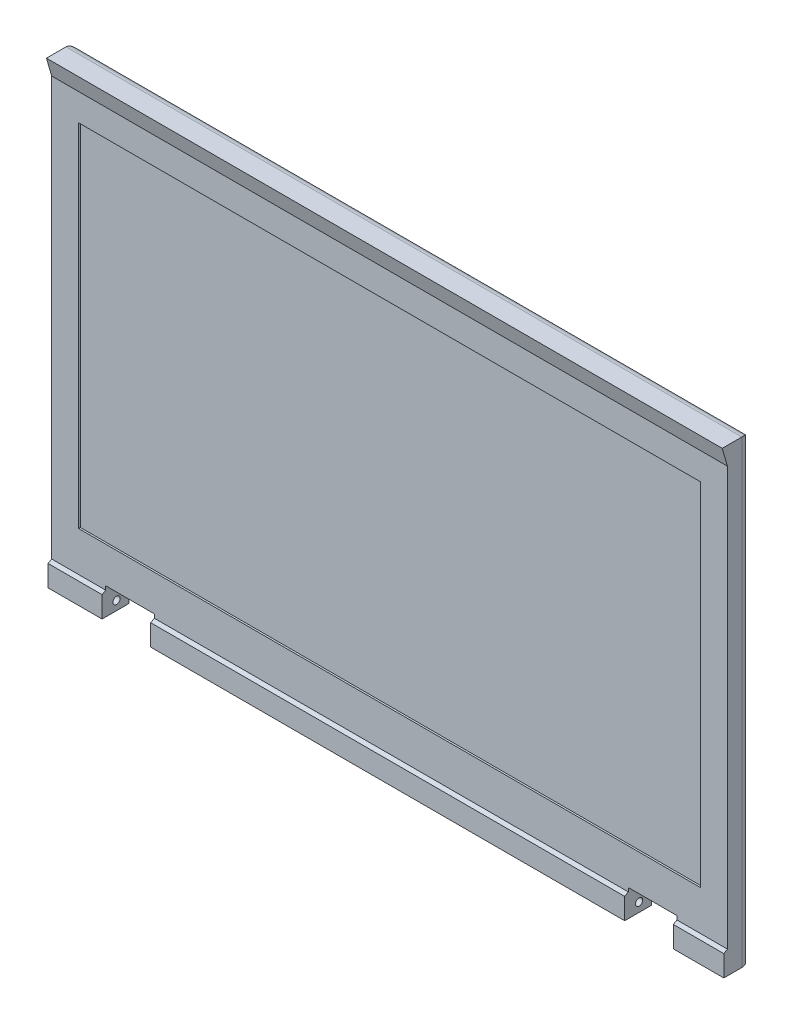
SolidWorks part; units mm, degrees
ref_plane "Front Plane" through (0, 0, 0) normal (0, 0, 1) x (1, 0, 0)
ref_plane "Top Plane" through (0, 0, 0) normal (0, 1, 0) x (1, 0, 0)
ref_plane "Right Plane" through (0, 0, 0) normal (1, 0, 0) x (0, 0, -1)
sketch "Sketch1" plane through (0, 0, 0) normal (1, 0, 0) x (0, 0, -1)
  line L1 (0, 0) -> (-13, 0)
  line L2 (0, 0) -> (0, 255)
  line L3 (0, 255) -> (-13, 255)
  line L4 (-13, 10) -> (-13, 255)
  line L5 (-13, 10) -> (-15, 10)
  line L7 (-13, 0) -> (-15, 0)
  line L8 (-15, 10) -> (-15, 0)
  dimension "D1" = 255
  dimension "D2" = 13
  dimension "D3" = 15
  dimension "D4" = 10
extrude "Boss-Extrude1" add sketch "Sketch1" along normal blind 375
sketch "Sketch2" plane through (0, 0, 13) normal (0, 0, 1) x (1, 0, 0)
  line L0 (375, 255) -> (0, 255) construction
  line L1 (15, 230) -> (360, 230)
  line L2 (15, 230) -> (15, 35)
  line L3 (15, 35) -> (360, 35)
  line L4 (360, 230) -> (360, 35)
  line L5 (375, 10) -> (0, 10) construction
  line L6 (0, 255) -> (0, 10) construction
  line L7 (375, 255) -> (375, 10) construction
  dimension "D1" = 25
  dimension "D2" = 25
  dimension "D3" = 15
  dimension "D4" = 15
extrude "Cut-Extrude1" cut sketch "Sketch2" against normal blind 1
chamfer "Chamfer1" distance 5 angle 30 1 edges at (187.5, 10, 13) first distance on face at (187.5, 10, 14)
sketch "Sketch3" plane through (0, 0, 15) normal (0, 0, 1) x (1, 0, 0)
  line L0 (375, 0) -> (0, 0) construction
  line L1 (30, 0) -> (57, 0)
  line L2 (30, 0) -> (30, 15)
  line L3 (30, 15) -> (57, 15)
  line L4 (57, 0) -> (57, 15)
  line L5 (0, 11.7321) -> (0, 0) construction
  line L6 (320, 0) -> (347, 0)
  line L7 (320, 0) -> (320, 15)
  line L8 (320, 15) -> (347, 15)
  line L9 (347, 0) -> (347, 15)
  line L10 (375, 11.7321) -> (375, 0) construction
  dimension "D1" = 30
  dimension "D2" = 28
  dimension "D3" = 27
  dimension "D4" = 27
  dimension "D5" = 15
  dimension "D6" = 15
extrude "Cut-Extrude2" cut sketch "Sketch3" against normal blind 30
sketch "Sketch4" plane through (57, 0, 0) normal (-1, 0, 0) x (0, 0, 1)
  line L0 (15, 0) -> (0, 0) construction
  line L1 (0, 0) -> (0, 255) construction
  circle A0 centre (7, 5) radius 2
  dimension "D1" = 4
  dimension "D2" = 5
  dimension "D3" = 7
extrude "Cut-Extrude3" cut sketch "Sketch4" against normal blind 300 and the other way blind 40
sketch "Sketch5" plane through (375, 0, 0) normal (1, 0, 0) x (0, 0, -1)
  line L0 (-13, 245) -> (-15.8675, 255)
  line L1 (-13, 255) -> (-13, 12.8868) construction
  line L2 (-15.8675, 255) -> (-13, 255)
  line L3 (-13, 255) -> (-13, 245)
  dimension "D1" = 10
  dimension "D2" = 16
extrude "Boss-Extrude2" add sketch "Sketch5" against normal blind 375
fillet "Fillet1" radius 5 3 edges at (0, 127.5, 0) (375, 127.5, 0) (187.5, 255, 0)
